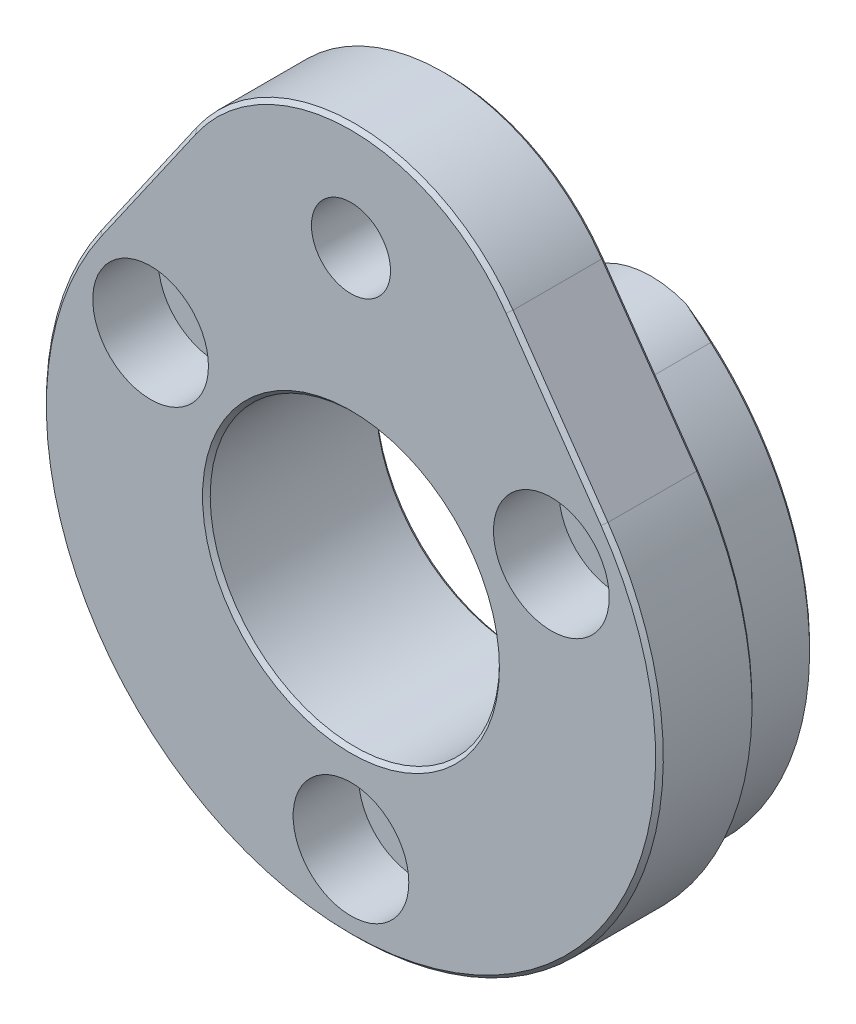
SolidWorks part; units mm, degrees
material "6061 合金"
ref_plane "前视基准面" through (0, 0, 0) normal (0, 0, 1) x (1, 0, 0)
ref_plane "上视基准面" through (0, 0, 0) normal (0, 1, 0) x (1, 0, 0)
ref_plane "右视基准面" through (0, 0, 0) normal (1, 0, 0) x (0, 0, -1)
other "Configuration Table"
sketch "草图1" plane through (0, 0, 0) normal (0, 0, 1) x (1, 0, 0)
  line L0 (0, 0) -> (0, 15) construction
  line L1 (0, 15) -> (0, 28) construction
  line L2 (0, 28) -> (13.1304, 9.1429)
  line L3 (0, 28) -> (-13.1304, 9.1429)
  line L4 (0, 0) -> (0, -16) construction
  line L5 (10.3923, -6) -> (0, 0) construction
  circle A0 centre (0, 0) radius 16 construction
  circle A1 centre (0, 15) radius 2.05
  arc A2 (-13.1304, 9.1429) -> (13.1304, 9.1429) centre (0, 0) ccw
  circle A3 centre (0, 0) radius 12 construction
  circle A9 centre (0, 0) radius 7.5
  dimension "D1" = 32
  dimension "D3" = 4.1
  dimension "D5" = 24
  dimension "D9" = 15
  dimension "D2" = 15
  dimension "D4" = 13
  dimension "D7" = 60
extrude "凸台-拉伸1" add sketch "草图1" along normal blind 5
fillet "圆角1" radius 10 1 edges at (0, 28, 2.5)
sketch "草图6" plane through (0, 0, 0) normal (0, 0, -1) x (-1, 0, 0)
  line L0 (0, 0) -> (-10.3923, -6) construction
  line L2 (0, 0) -> (10.3923, -6) construction
  line L3 (0, 0) -> (0, -16) construction
  circle A4 centre (0, 0) radius 7.5
  arc A5 (-13.1304, 9.1429) -> (13.1304, 9.1429) centre (0, 0) ccw construction
  circle A6 centre (0, 0) radius 14.99
  dimension "D3" = 15
  dimension "D4" = 29.98
  dimension "D5" = 60
  dimension "D6" = 60
  dimension "D7" = 12
  dimension "D8" = 12
extrude "凸台-拉伸2" add sketch "草图6" along normal blind 4
sketch "草图2" plane through (0, 0, 5) normal (0, 0, 1) x (1, 0, 0)
  line L0 (0, 0) -> (0, -16) construction
  arc A0 (-13.1304, 9.1429) -> (13.1304, 9.1429) centre (0, 0) ccw construction
  point P6 (0, -12)
  point P7 (-10.3923, 6)
  point P10 (10.3923, 6)
  dimension "D1" = 12
  dimension "D2" = 3
hole_wizard "M3 六角圆柱头螺钉的柱形沉头孔2" positions "草图2" profile "草图3" counterbore size "M3" standard "GB" end condition up to next
sketch "草图3" plane through (10.3923, 6, 5) normal (1, 0, 0) x (0, -1, 0)
  line L0 (0, 0) -> (0, 9)
  line L1 (0, 9) -> (1.6, 9)
  line L3 (1.6, 9) -> (1.6, 3.4)
  line L4 (1.6, 3.4) -> (3, 3.4)
  line L5 (3, 3.4) -> (3, 0)
  line L7 (3, 0) -> (0, 0)
  line L11 (0, -6.35) -> (0, 107.95) construction
  dimension "通孔孔直径" = 3.2
  dimension "通孔孔深度" = 9
  dimension "柱形沉头孔直径" = 6
  dimension "柱形沉头孔深度" = 3.4
sketch "草图8" plane through (0, 0, -4) normal (0, 0, -1) x (-1, 0, 0)
  circle A0 centre (0.081, 14.9898) radius 5
  circle A1 centre (0, 0) radius 14.99 construction
  dimension "D1" = 10
extrude "切除-拉伸1" cut sketch "草图8" against normal up to surface (4 mm away) up to face at (0, 1.03, 0)
sketch "草图4" plane through (0, 0, 0) normal (0, 0, -1) x (-1, 0, 0)
  circle A2 centre (0, 15) radius 3.75
  dimension "D1" = 7.5
chamfer "倒角1" distance 0.2 angle 45 11 edges at (0, -16, 0) (-10.6685, 12.6786, 0) (10.6685, 12.6786, 0) (0, 20.5, 0) (0, 20.5, 5) (-10.6685, 12.6786, 5) (10.6685, 12.6786, 5) (0, -16, 5) (7.5, 0, 5) (-7.5, 0, -4) (0.081, -14.9898, -4)
extrude "切除-拉伸2" cut sketch "草图4" against normal blind 2.05
fillet "圆角2" radius 5 2 edges at (-5.0064, 14.1293, -1.9) (4.8535, 14.1825, -1.9)
chamfer "倒角3" [suppressed] distance 0.5 angle 45
sketch "草图9" plane through (0, 0, -4) normal (0, 0, -1) x (-1, 0, 0)
  line L0 (0, 0) -> (10.3923, -6) construction
  line L1 (0, 0) -> (0, -12) construction
  line L2 (0, 0) -> (-10.3923, -6) construction
  circle A0 centre (0, 0) radius 12 construction
  point P7 (10.3923, -6)
  point P8 (-10.3923, -6)
  dimension "D1" = 24
  dimension "D2" = 60
  dimension "D3" = 60
hole_wizard "Ø3.0mm 暗销孔1" positions "草图9" profile "草图10" hole size "Ø3.0" standard "GB"
sketch "草图10" plane through (10.3923, -6, -4) normal (1, 0, 0) x (0, 1, 0)
  line L0 (0, 0) -> (0, 4.9013)
  line L1 (0, 4.9013) -> (1.5, 4)
  line L2 (1.5, 4) -> (1.5, 0)
  line L5 (1.5, 0) -> (0, 0)
  line L10 (0, 4.9013) -> (-1.5, 4) construction
  line L11 (0, -6.35) -> (0, 107.95) construction
  dimension "孔直径" = 3
  dimension "孔深度" = 4
  dimension "导头角度" = 118
sketch "草图11" plane through (0, 0, 5) normal (0, 0, 1) x (1, 0, 0)
  circle A0 centre (0, 15) radius 3.05
  dimension "D1" = 6.1
extrude "切除-拉伸3" [suppressed] cut sketch "草图11" against normal blind 2
chamfer "倒角4" [suppressed] distance 0.2 angle 45
chamfer "倒角5" distance 0.2 angle 45 1 edges at (-3.75, 15, 0)
